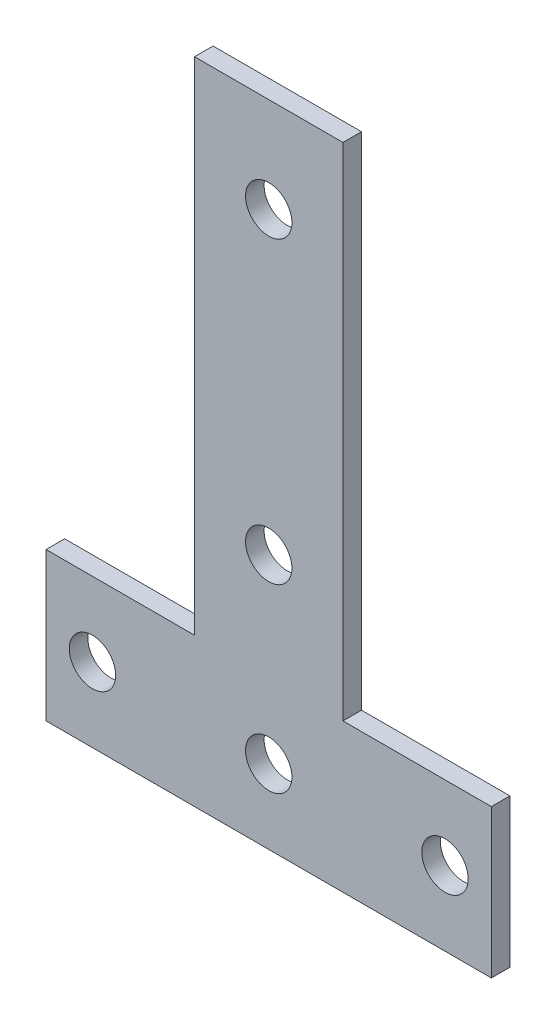
SolidWorks part; units mm, degrees
ref_plane "Front plane" through (0, 0, 0) normal (0, 0, 1) x (1, 0, 0)
ref_plane "Top plane" through (0, 0, 0) normal (0, 1, 0) x (1, 0, 0)
ref_plane "Right plane" through (0, 0, 0) normal (1, 0, 0) x (0, 0, -1)
ref_axis "Axis X" through (0, 0, 0) along (1, 0, 0)
ref_axis "Axis Y" through (0, 0, 0) along (0, 1, 0)
ref_axis "Axis Z" through (0, 0, 0) along (0, 0, 1)
sketch "Sketch2" plane through (0, 0, 0) normal (0, 0, 1) x (1, 0, 0)
  line L0 (-8, 0) -> (-8, 54)
  line L1 (-8, 54) -> (8, 54)
  line L2 (8, 54) -> (8, 0)
  line L3 (8, 0) -> (24, 0)
  line L4 (24, 0) -> (24, -16)
  line L5 (24, -16) -> (-24, -16)
  line L6 (-24, -16) -> (-24, 0)
  line L7 (-24, 0) -> (-8, 0)
  line L8 (0, 54) -> (0, -17.8356) construction
  line L9 (-24, -8) -> (24, -8) construction
  circle A1 centre (19, -8) radius 2.5
  circle A2 centre (0, -8) radius 2.5
  circle A3 centre (-19, -8) radius 2.5
  circle A4 centre (0, 43.75) radius 2.5
  circle A5 centre (0, 11.5) radius 2.5
  dimension "D6" = 5
  dimension "D7" = 5
  dimension "D8" = 5
  dimension "D9" = 5
  dimension "D1" = 48
  dimension "D2" = 70
  dimension "D3" = 16
  dimension "D4" = 16
  dimension "D5" = 5
  dimension "D10" = 10.25
  dimension "D11" = 42.5
extrude "Extrude1" add sketch "Sketch2" along normal blind 2
